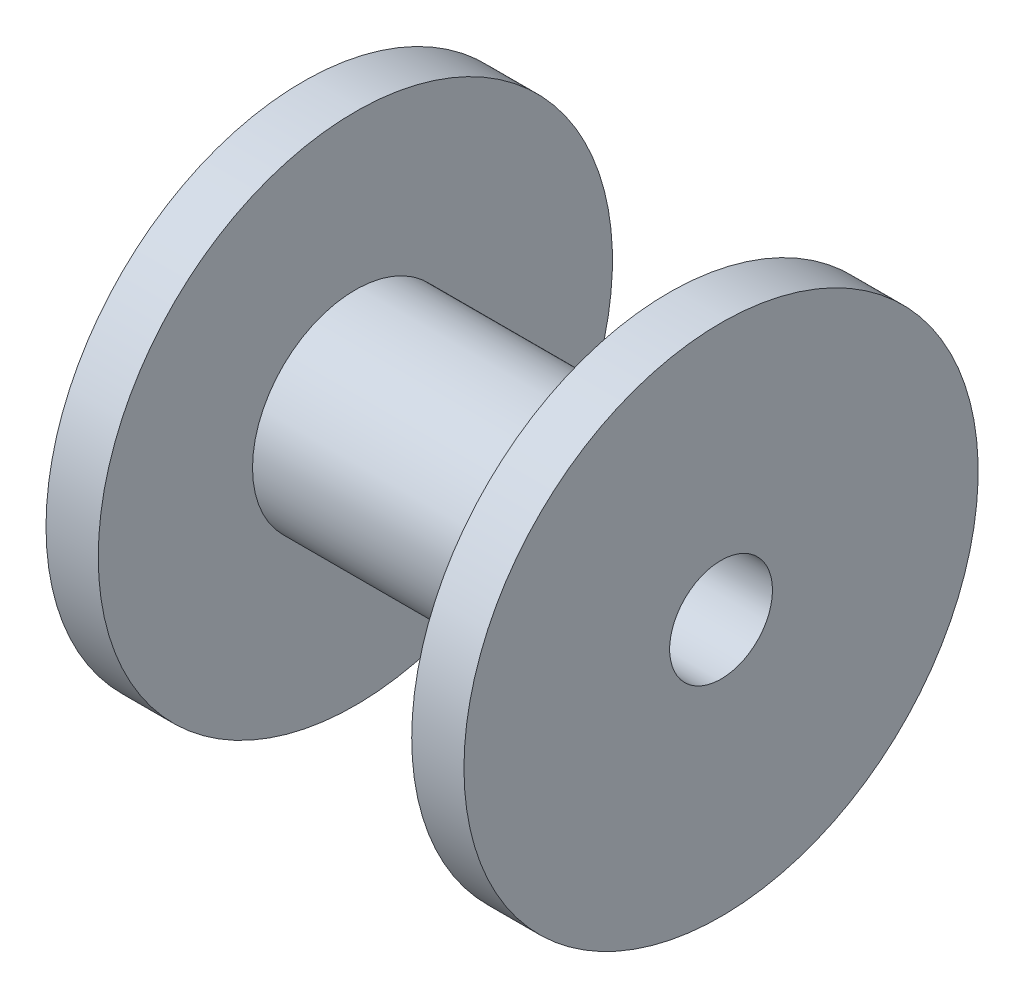
SolidWorks part; units mm, degrees
ref_plane "Front Plane" through (0, 0, 0) normal (0, 0, 1) x (1, 0, 0)
ref_plane "Top Plane" through (0, 0, 0) normal (0, 1, 0) x (1, 0, 0)
ref_plane "Right Plane" through (0, 0, 0) normal (1, 0, 0) x (0, 0, -1)
sketch "Sketch1" plane through (0, 0, 0) normal (0, 0, 1) x (1, 0, 0)
  line L0 (0, 0) -> (40.64, 0)
  line L1 (0, 0) -> (0, -25)
  line L2 (5.08, -25) -> (0, -25)
  line L3 (5.08, -25) -> (5.08, -10)
  line L4 (5.08, -10) -> (35.56, -10)
  line L5 (35.56, -10) -> (35.56, -25)
  line L6 (35.56, -25) -> (40.64, -25)
  line L7 (40.64, -25) -> (40.64, 0)
  dimension "D1" = 40.64
  dimension "D2" = 10
  dimension "D3" = 15
  dimension "0.2in" = 5.08
  dimension "D4" = 30.48
revolve "Revolve1" add sketch "Sketch1" angle 360 about L0
sketch "Sketch2" plane through (40.64, 0, 0) normal (1, 0, 0) x (0, 0, -1)
  circle A0 centre (0, 0) radius 5
extrude "Cut-Extrude1" cut sketch "Sketch2" against normal blind 40.64
